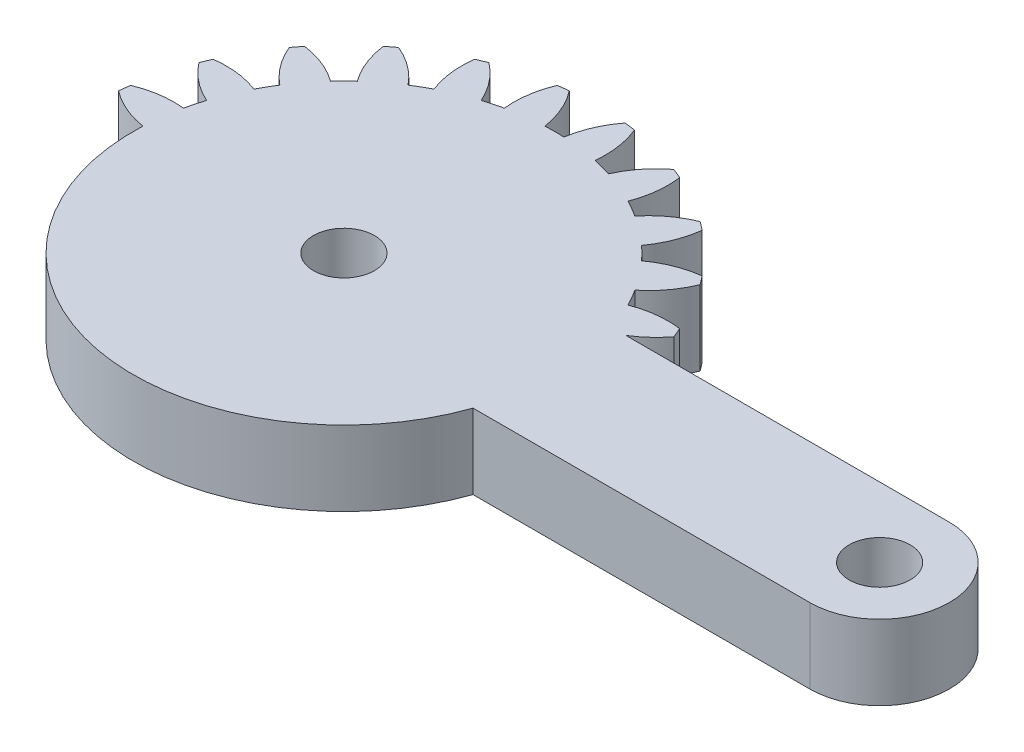
SolidWorks part; units mm, degrees
ref_plane "Front Plane" through (0, 0, 0) normal (0, 0, 1) x (1, 0, 0)
ref_plane "Top Plane" through (0, 0, 0) normal (0, 1, 0) x (1, 0, 0)
ref_plane "Right Plane" through (0, 0, 0) normal (1, 0, 0) x (0, 0, -1)
sketch "Sketch1" plane through (0, 0, 0) normal (0, 1, 0) x (1, 0, 0)
  line L0 (20.6437, 4) -> (2.0816, 4)
  line L1 (2.0816, -4) -> (20.6437, -4)
  arc A0 (2.0816, 4) -> (3.5217, 5.3071) centre (-0.7683, 8.5867) ccw
  arc A1 (3.5217, 5.3071) -> (3.2829, 5.8838) centre (-10.1063, 0) ccw
  arc A2 (3.2829, 5.8838) -> (0.6271, 5.5703) centre (2.5684, 0.5313) ccw
  arc A3 (0.6271, 5.5703) -> (0.0844, 6.5103) centre (-10.1063, 0) ccw
  arc A4 (0.0844, 6.5103) -> (1.6838, 8.6535) centre (-3.3089, 10.711) ccw
  arc A5 (1.6838, 8.6535) -> (1.3038, 9.1487) centre (-10.1063, 0) ccw
  arc A6 (1.3038, 9.1487) -> (-1.1803, 8.1585) centre (1.999, 3.7936) ccw
  arc A7 (-1.1803, 8.1585) -> (-1.9479, 8.926) centre (-10.1063, 0) ccw
  arc A8 (-1.9479, 8.926) -> (-0.9576, 11.4102) centre (-6.3127, 12.1053) ccw
  arc A9 (-0.9576, 11.4102) -> (-1.4528, 11.7901) centre (-10.1063, 0) ccw
  arc A10 (-1.4528, 11.7901) -> (-3.596, 10.1907) centre (0.6046, 6.7975) ccw
  arc A11 (-3.596, 10.1907) -> (-4.5361, 10.7334) centre (-10.1063, 0) ccw
  arc A12 (-4.5361, 10.7334) -> (-4.2225, 13.3892) centre (-9.5751, 12.6747) ccw
  arc A13 (-4.2225, 13.3892) -> (-4.7992, 13.6281) centre (-10.1063, 0) ccw
  arc A14 (-4.7992, 13.6281) -> (-6.4554, 11.5285) centre (-1.5196, 9.3381) ccw
  arc A15 (-6.4554, 11.5285) -> (-7.5039, 11.8094) centre (-10.1063, 0) ccw
  arc A16 (-7.5039, 11.8094) -> (-7.8884, 14.4558) centre (-12.8736, 12.3803) ccw
  arc A17 (-7.8884, 14.4558) -> (-8.5072, 14.5373) centre (-10.1063, 0) ccw
  arc A18 (-8.5072, 14.5373) -> (-9.5636, 12.0806) centre (-4.2291, 11.2423) ccw
  arc A19 (-9.5636, 12.0806) -> (-10.6491, 12.0806) centre (-10.1063, 0) ccw
  arc A20 (-10.6491, 12.0806) -> (-11.7054, 14.5373) centre (-15.9836, 11.2423) ccw
  arc A21 (-11.7054, 14.5373) -> (-12.3243, 14.4558) centre (-10.1063, 0) ccw
  arc A22 (-12.3243, 14.4558) -> (-12.7088, 11.8094) centre (-7.3391, 12.3803) ccw
  arc A23 (-12.7088, 11.8094) -> (-13.7573, 11.5285) centre (-10.1063, 0) ccw
  arc A24 (-13.7573, 11.5285) -> (-15.4135, 13.6281) centre (-18.6931, 9.3381) ccw
  arc A25 (-15.4135, 13.6281) -> (-15.9901, 13.3892) centre (-10.1063, 0) ccw
  arc A26 (-15.9901, 13.3892) -> (-15.6766, 10.7334) centre (-10.6376, 12.6747) ccw
  arc A27 (-15.6766, 10.7334) -> (-16.6166, 10.1907) centre (-10.1063, 0) ccw
  arc A28 (-16.6166, 10.1907) -> (-18.7599, 11.7901) centre (-20.8173, 6.7975) ccw
  arc A29 (-18.7599, 11.7901) -> (-19.255, 11.4102) centre (-10.1063, 0) ccw
  arc A30 (-19.255, 11.4102) -> (-18.2648, 8.926) centre (-13.9, 12.1053) ccw
  arc A31 (-18.2648, 8.926) -> (-19.0324, 8.1585) centre (-10.1063, 0) ccw
  arc A32 (-19.0324, 8.1585) -> (-21.5165, 9.1487) centre (-22.2117, 3.7936) ccw
  arc A33 (-21.5165, 9.1487) -> (-21.8965, 8.6535) centre (-10.1063, 0) ccw
  arc A34 (-21.8965, 8.6535) -> (-20.2971, 6.5103) centre (-16.9038, 10.711) ccw
  arc A35 (-20.2971, 6.5103) -> (-20.8398, 5.5703) centre (-10.1063, 0) ccw
  arc A36 (-20.8398, 5.5703) -> (-23.4956, 5.8838) centre (-22.7811, 0.5313) ccw
  arc A37 (-23.4956, 5.8838) -> (-23.7344, 5.3071) centre (-10.1063, 0) ccw
  arc A38 (-23.7344, 5.3071) -> (-21.6348, 3.6509) centre (-19.4444, 8.5867) ccw
  arc A39 (-21.6348, 3.6509) -> (-21.9157, 2.6025) centre (-10.1063, 0) ccw
  arc A40 (-21.9157, 2.6025) -> (-24.5622, 2.2179) centre (-22.4867, -2.7673) ccw
  arc A41 (-24.5622, 2.2179) -> (-24.6437, 1.5991) centre (-10.1063, 0) ccw
  arc A42 (-24.6437, 1.5991) -> (-22.1869, 0.5427) centre (-21.3486, 5.8773) ccw
  arc A43 (-22.1869, 0.5427) -> (-22.1869, -0.5427) centre (-10.1063, 0) ccw
  arc A44 (-22.1869, -0.5427) -> (-24.6437, -1.5991) centre (-21.3486, -5.8773) ccw
  arc A45 (-24.6437, -1.5991) -> (-24.5622, -2.2179) centre (-10.1063, 0) ccw
  arc A46 (-24.5622, -2.2179) -> (-21.9157, -2.6025) centre (-22.4867, 2.7673) ccw
  arc A47 (-21.9157, -2.6025) -> (-21.6348, -3.6509) centre (-10.1063, 0) ccw
  arc A48 (-21.6348, -3.6509) -> (-23.7344, -5.3071) centre (-19.4444, -8.5867) ccw
  arc A49 (-23.7344, -5.3071) -> (-23.4956, -5.8838) centre (-10.1063, 0) ccw
  arc A50 (-23.4956, -5.8838) -> (-20.8398, -5.5703) centre (-22.7811, -0.5313) ccw
  arc A51 (-20.8398, -5.5703) -> (-20.2971, -6.5103) centre (-10.1063, 0) ccw
  arc A52 (-20.2971, -6.5103) -> (-21.8965, -8.6535) centre (-16.9038, -10.711) ccw
  arc A53 (-21.8965, -8.6535) -> (-21.5165, -9.1487) centre (-10.1063, 0) ccw
  arc A54 (-21.5165, -9.1487) -> (-19.0324, -8.1585) centre (-22.2117, -3.7936) ccw
  arc A55 (-19.0324, -8.1585) -> (-18.2648, -8.926) centre (-10.1063, 0) ccw
  arc A56 (-18.2648, -8.926) -> (-19.255, -11.4102) centre (-13.9, -12.1053) ccw
  arc A57 (-19.255, -11.4102) -> (-18.7599, -11.7901) centre (-10.1063, 0) ccw
  arc A58 (-18.7599, -11.7901) -> (-16.6166, -10.1907) centre (-20.8173, -6.7975) ccw
  arc A59 (-16.6166, -10.1907) -> (-15.6766, -10.7334) centre (-10.1063, 0) ccw
  arc A60 (-15.6766, -10.7334) -> (-15.9901, -13.3892) centre (-10.6376, -12.6747) ccw
  arc A61 (-15.9901, -13.3892) -> (-15.4135, -13.6281) centre (-10.1063, 0) ccw
  arc A62 (-15.4135, -13.6281) -> (-13.7573, -11.5285) centre (-18.6931, -9.3381) ccw
  arc A63 (-13.7573, -11.5285) -> (-12.7088, -11.8094) centre (-10.1063, 0) ccw
  arc A64 (-12.7088, -11.8094) -> (-12.3243, -14.4558) centre (-7.3391, -12.3803) ccw
  arc A65 (-12.3243, -14.4558) -> (-11.7054, -14.5373) centre (-10.1063, 0) ccw
  arc A66 (-11.7054, -14.5373) -> (-10.6491, -12.0806) centre (-15.9836, -11.2423) ccw
  arc A67 (-10.6491, -12.0806) -> (-9.5636, -12.0806) centre (-10.1063, 0) ccw
  arc A68 (-9.5636, -12.0806) -> (-8.5072, -14.5373) centre (-4.2291, -11.2423) ccw
  arc A69 (-8.5072, -14.5373) -> (-7.8884, -14.4558) centre (-10.1063, 0) ccw
  arc A70 (-7.8884, -14.4558) -> (-7.5039, -11.8094) centre (-12.8736, -12.3803) ccw
  arc A71 (-7.5039, -11.8094) -> (-6.4554, -11.5285) centre (-10.1063, 0) ccw
  arc A72 (-6.4554, -11.5285) -> (-4.7992, -13.6281) centre (-1.5196, -9.3381) ccw
  arc A73 (-4.7992, -13.6281) -> (-4.2225, -13.3892) centre (-10.1063, 0) ccw
  arc A74 (-4.2225, -13.3892) -> (-4.5361, -10.7334) centre (-9.5751, -12.6747) ccw
  arc A75 (-4.5361, -10.7334) -> (-3.596, -10.1907) centre (-10.1063, 0) ccw
  arc A76 (-3.596, -10.1907) -> (-1.4528, -11.7901) centre (0.6046, -6.7975) ccw
  arc A77 (-1.4528, -11.7901) -> (-0.9576, -11.4102) centre (-10.1063, 0) ccw
  arc A78 (-0.9576, -11.4102) -> (-1.9479, -8.926) centre (-6.3127, -12.1053) ccw
  arc A79 (-1.9479, -8.926) -> (-1.1803, -8.1585) centre (-10.1063, 0) ccw
  arc A80 (-1.1803, -8.1585) -> (1.3038, -9.1487) centre (1.999, -3.7936) ccw
  arc A81 (1.3038, -9.1487) -> (1.6838, -8.6535) centre (-10.1063, 0) ccw
  arc A82 (1.6838, -8.6535) -> (0.0844, -6.5103) centre (-3.3089, -10.711) ccw
  arc A83 (0.0844, -6.5103) -> (0.6271, -5.5703) centre (-10.1063, 0) ccw
  arc A84 (0.6271, -5.5703) -> (3.2829, -5.8838) centre (2.5684, -0.5313) ccw
  arc A85 (3.2829, -5.8838) -> (3.5217, -5.3071) centre (-10.1063, 0) ccw
  arc A86 (3.5217, -5.3071) -> (2.0816, -4) centre (-0.7683, -8.5867) ccw
  arc A87 (20.6437, -4) -> (20.6437, 4) centre (20.6437, 0) ccw
  circle A88 centre (-10.1063, 0) radius 1.75
  circle A89 centre (20.6437, 0) radius 1.75
  dimension "D1" = 3.5
  dimension "D2" = 3.5
extrude "Boss-Extrude1" add sketch "Sketch1" along normal blind 4.3
sketch "Sketch2" plane through (0, 4.3, 0) normal (0, 1, 0) x (1, 0, 0)
  line L0 (2.0816, -4) -> (1.3057, -4)
  line L2 (20.6437, 4) -> (2.0816, 4)
  line L3 (2.0816, -4) -> (20.6437, -4)
  line L4 (20.6437, 4) -> (2.0816, 4)
  line L5 (2.0816, -4) -> (20.6437, -4)
  circle A0 centre (-10.1063, 0) radius 12.0927
  arc A88 (20.6437, -4) -> (20.6437, 4) centre (20.6437, 0) ccw
  arc A89 (2.0816, 4) -> (3.5217, 5.3071) centre (-0.7683, 8.5867) ccw
  arc A90 (3.5217, 5.3071) -> (3.2829, 5.8838) centre (-10.1063, 0) ccw
  arc A91 (3.2829, 5.8838) -> (0.6271, 5.5703) centre (2.5684, 0.5313) ccw
  arc A92 (0.6271, 5.5703) -> (0.0844, 6.5103) centre (-10.1063, 0) ccw
  arc A93 (0.0844, 6.5103) -> (1.6838, 8.6535) centre (-3.3089, 10.711) ccw
  arc A94 (1.6838, 8.6535) -> (1.3038, 9.1487) centre (-10.1063, 0) ccw
  arc A95 (1.3038, 9.1487) -> (-1.1803, 8.1585) centre (1.999, 3.7936) ccw
  arc A96 (-1.1803, 8.1585) -> (-1.9479, 8.926) centre (-10.1063, 0) ccw
  arc A97 (-1.9479, 8.926) -> (-0.9576, 11.4102) centre (-6.3127, 12.1053) ccw
  arc A98 (-0.9576, 11.4102) -> (-1.4528, 11.7901) centre (-10.1063, 0) ccw
  arc A99 (-1.4528, 11.7901) -> (-3.596, 10.1907) centre (0.6046, 6.7975) ccw
  arc A100 (-3.596, 10.1907) -> (-4.5361, 10.7334) centre (-10.1063, 0) ccw
  arc A101 (-4.5361, 10.7334) -> (-4.2225, 13.3892) centre (-9.5751, 12.6747) ccw
  arc A102 (-4.2225, 13.3892) -> (-4.7992, 13.6281) centre (-10.1063, 0) ccw
  arc A103 (-4.7992, 13.6281) -> (-6.4554, 11.5285) centre (-1.5196, 9.3381) ccw
  arc A104 (-6.4554, 11.5285) -> (-7.5039, 11.8094) centre (-10.1063, 0) ccw
  arc A105 (-7.5039, 11.8094) -> (-7.8884, 14.4558) centre (-12.8736, 12.3803) ccw
  arc A106 (-7.8884, 14.4558) -> (-8.5072, 14.5373) centre (-10.1063, 0) ccw
  arc A107 (-8.5072, 14.5373) -> (-9.5636, 12.0806) centre (-4.2291, 11.2423) ccw
  arc A108 (-9.5636, 12.0806) -> (-10.6491, 12.0806) centre (-10.1063, 0) ccw
  arc A109 (-10.6491, 12.0806) -> (-11.7054, 14.5373) centre (-15.9836, 11.2423) ccw
  arc A110 (-11.7054, 14.5373) -> (-12.3243, 14.4558) centre (-10.1063, 0) ccw
  arc A111 (-12.3243, 14.4558) -> (-12.7088, 11.8094) centre (-7.3391, 12.3803) ccw
  arc A112 (-12.7088, 11.8094) -> (-13.7573, 11.5285) centre (-10.1063, 0) ccw
  arc A113 (-13.7573, 11.5285) -> (-15.4135, 13.6281) centre (-18.6931, 9.3381) ccw
  arc A114 (-15.4135, 13.6281) -> (-15.9901, 13.3892) centre (-10.1063, 0) ccw
  arc A115 (-15.9901, 13.3892) -> (-15.6766, 10.7334) centre (-10.6376, 12.6747) ccw
  arc A116 (-15.6766, 10.7334) -> (-16.6166, 10.1907) centre (-10.1063, 0) ccw
  arc A117 (-16.6166, 10.1907) -> (-18.7599, 11.7901) centre (-20.8173, 6.7975) ccw
  arc A118 (-18.7599, 11.7901) -> (-19.255, 11.4102) centre (-10.1063, 0) ccw
  arc A119 (-19.255, 11.4102) -> (-18.2648, 8.926) centre (-13.9, 12.1053) ccw
  arc A120 (-18.2648, 8.926) -> (-19.0324, 8.1585) centre (-10.1063, 0) ccw
  arc A121 (-19.0324, 8.1585) -> (-21.5165, 9.1487) centre (-22.2117, 3.7936) ccw
  arc A122 (-21.5165, 9.1487) -> (-21.8965, 8.6535) centre (-10.1063, 0) ccw
  arc A123 (-21.8965, 8.6535) -> (-20.2971, 6.5103) centre (-16.9038, 10.711) ccw
  arc A124 (-20.2971, 6.5103) -> (-20.8398, 5.5703) centre (-10.1063, 0) ccw
  arc A125 (-20.8398, 5.5703) -> (-23.4956, 5.8838) centre (-22.7811, 0.5313) ccw
  arc A126 (-23.4956, 5.8838) -> (-23.7344, 5.3071) centre (-10.1063, 0) ccw
  arc A127 (-23.7344, 5.3071) -> (-21.6348, 3.6509) centre (-19.4444, 8.5867) ccw
  arc A128 (-21.6348, 3.6509) -> (-21.9157, 2.6025) centre (-10.1063, 0) ccw
  arc A129 (-21.9157, 2.6025) -> (-24.5622, 2.2179) centre (-22.4867, -2.7673) ccw
  arc A130 (-24.5622, 2.2179) -> (-24.6437, 1.5991) centre (-10.1063, 0) ccw
  arc A131 (-24.6437, 1.5991) -> (-22.1869, 0.5427) centre (-21.3486, 5.8773) ccw
  arc A132 (-22.1869, 0.5427) -> (-22.1869, -0.5427) centre (-10.1063, 0) ccw
  arc A133 (-22.1869, -0.5427) -> (-24.6437, -1.5991) centre (-21.3486, -5.8773) ccw
  arc A134 (-24.6437, -1.5991) -> (-24.5622, -2.2179) centre (-10.1063, 0) ccw
  arc A135 (-24.5622, -2.2179) -> (-21.9157, -2.6025) centre (-22.4867, 2.7673) ccw
  arc A136 (-21.9157, -2.6025) -> (-21.6348, -3.6509) centre (-10.1063, 0) ccw
  arc A137 (-21.6348, -3.6509) -> (-23.7344, -5.3071) centre (-19.4444, -8.5867) ccw
  arc A138 (-23.7344, -5.3071) -> (-23.4956, -5.8838) centre (-10.1063, 0) ccw
  arc A139 (-23.4956, -5.8838) -> (-20.8398, -5.5703) centre (-22.7811, -0.5313) ccw
  arc A140 (-20.8398, -5.5703) -> (-20.2971, -6.5103) centre (-10.1063, 0) ccw
  arc A141 (-20.2971, -6.5103) -> (-21.8965, -8.6535) centre (-16.9038, -10.711) ccw
  arc A142 (-21.8965, -8.6535) -> (-21.5165, -9.1487) centre (-10.1063, 0) ccw
  arc A143 (-21.5165, -9.1487) -> (-19.0324, -8.1585) centre (-22.2117, -3.7936) ccw
  arc A144 (-19.0324, -8.1585) -> (-18.2648, -8.926) centre (-10.1063, 0) ccw
  arc A145 (-18.2648, -8.926) -> (-19.255, -11.4102) centre (-13.9, -12.1053) ccw
  arc A146 (-19.255, -11.4102) -> (-18.7599, -11.7901) centre (-10.1063, 0) ccw
  arc A147 (-18.7599, -11.7901) -> (-16.6166, -10.1907) centre (-20.8173, -6.7975) ccw
  arc A148 (-16.6166, -10.1907) -> (-15.6766, -10.7334) centre (-10.1063, 0) ccw
  arc A149 (-15.6766, -10.7334) -> (-15.9901, -13.3892) centre (-10.6376, -12.6747) ccw
  arc A150 (-15.9901, -13.3892) -> (-15.4135, -13.6281) centre (-10.1063, 0) ccw
  arc A151 (-15.4135, -13.6281) -> (-13.7573, -11.5285) centre (-18.6931, -9.3381) ccw
  arc A152 (-13.7573, -11.5285) -> (-12.7088, -11.8094) centre (-10.1063, 0) ccw
  arc A153 (-12.7088, -11.8094) -> (-12.3243, -14.4558) centre (-7.3391, -12.3803) ccw
  arc A154 (-12.3243, -14.4558) -> (-11.7054, -14.5373) centre (-10.1063, 0) ccw
  arc A155 (-11.7054, -14.5373) -> (-10.6491, -12.0806) centre (-15.9836, -11.2423) ccw
  arc A156 (-10.6491, -12.0806) -> (-9.5636, -12.0806) centre (-10.1063, 0) ccw
  arc A157 (-9.5636, -12.0806) -> (-8.5072, -14.5373) centre (-4.2291, -11.2423) ccw
  arc A158 (-8.5072, -14.5373) -> (-7.8884, -14.4558) centre (-10.1063, 0) ccw
  arc A159 (-7.8884, -14.4558) -> (-7.5039, -11.8094) centre (-12.8736, -12.3803) ccw
  arc A160 (-7.5039, -11.8094) -> (-6.4554, -11.5285) centre (-10.1063, 0) ccw
  arc A161 (-6.4554, -11.5285) -> (-4.7992, -13.6281) centre (-1.5196, -9.3381) ccw
  arc A162 (-4.7992, -13.6281) -> (-4.2225, -13.3892) centre (-10.1063, 0) ccw
  arc A163 (-4.2225, -13.3892) -> (-4.5361, -10.7334) centre (-9.5751, -12.6747) ccw
  arc A164 (-4.5361, -10.7334) -> (-3.596, -10.1907) centre (-10.1063, 0) ccw
  arc A165 (-3.596, -10.1907) -> (-1.4528, -11.7901) centre (0.6046, -6.7975) ccw
  arc A166 (-1.4528, -11.7901) -> (-0.9576, -11.4102) centre (-10.1063, 0) ccw
  arc A167 (-0.9576, -11.4102) -> (-1.9479, -8.926) centre (-6.3127, -12.1053) ccw
  arc A168 (-1.9479, -8.926) -> (-1.1803, -8.1585) centre (-10.1063, 0) ccw
  arc A169 (-1.1803, -8.1585) -> (1.3038, -9.1487) centre (1.999, -3.7936) ccw
  arc A170 (1.3038, -9.1487) -> (1.6838, -8.6535) centre (-10.1063, 0) ccw
  arc A171 (1.6838, -8.6535) -> (0.0844, -6.5103) centre (-3.3089, -10.711) ccw
  arc A172 (0.0844, -6.5103) -> (0.6271, -5.5703) centre (-10.1063, 0) ccw
  arc A173 (0.6271, -5.5703) -> (3.2829, -5.8838) centre (2.5684, -0.5313) ccw
  arc A174 (3.2829, -5.8838) -> (3.5217, -5.3071) centre (-10.1063, 0) ccw
  arc A175 (3.5217, -5.3071) -> (2.0816, -4) centre (-0.7683, -8.5867) ccw
  arc A176 (20.6437, -4) -> (20.6437, 4) centre (20.6437, 0) ccw
  arc A177 (2.0816, 4) -> (3.5217, 5.3071) centre (-0.7683, 8.5867) ccw
  arc A178 (3.5217, 5.3071) -> (3.2829, 5.8838) centre (-10.1063, 0) ccw
  arc A179 (3.2829, 5.8838) -> (0.6271, 5.5703) centre (2.5684, 0.5313) ccw
  arc A180 (0.6271, 5.5703) -> (0.0844, 6.5103) centre (-10.1063, 0) ccw
  arc A181 (0.0844, 6.5103) -> (1.6838, 8.6535) centre (-3.3089, 10.711) ccw
  arc A182 (1.6838, 8.6535) -> (1.3038, 9.1487) centre (-10.1063, 0) ccw
  arc A183 (1.3038, 9.1487) -> (-1.1803, 8.1585) centre (1.999, 3.7936) ccw
  arc A184 (-1.1803, 8.1585) -> (-1.9479, 8.926) centre (-10.1063, 0) ccw
  arc A185 (-1.9479, 8.926) -> (-0.9576, 11.4102) centre (-6.3127, 12.1053) ccw
  arc A186 (-0.9576, 11.4102) -> (-1.4528, 11.7901) centre (-10.1063, 0) ccw
  arc A187 (-1.4528, 11.7901) -> (-3.596, 10.1907) centre (0.6046, 6.7975) ccw
  arc A188 (-3.596, 10.1907) -> (-4.5361, 10.7334) centre (-10.1063, 0) ccw
  arc A189 (-4.5361, 10.7334) -> (-4.2225, 13.3892) centre (-9.5751, 12.6747) ccw
  arc A190 (-4.2225, 13.3892) -> (-4.7992, 13.6281) centre (-10.1063, 0) ccw
  arc A191 (-4.7992, 13.6281) -> (-6.4554, 11.5285) centre (-1.5196, 9.3381) ccw
  arc A192 (-6.4554, 11.5285) -> (-7.5039, 11.8094) centre (-10.1063, 0) ccw
  arc A193 (-7.5039, 11.8094) -> (-7.8884, 14.4558) centre (-12.8736, 12.3803) ccw
  arc A194 (-7.8884, 14.4558) -> (-8.5072, 14.5373) centre (-10.1063, 0) ccw
  arc A195 (-8.5072, 14.5373) -> (-9.5636, 12.0806) centre (-4.2291, 11.2423) ccw
  arc A196 (-9.5636, 12.0806) -> (-10.6491, 12.0806) centre (-10.1063, 0) ccw
  arc A197 (-10.6491, 12.0806) -> (-11.7054, 14.5373) centre (-15.9836, 11.2423) ccw
  arc A198 (-11.7054, 14.5373) -> (-12.3243, 14.4558) centre (-10.1063, 0) ccw
  arc A199 (-12.3243, 14.4558) -> (-12.7088, 11.8094) centre (-7.3391, 12.3803) ccw
  arc A200 (-12.7088, 11.8094) -> (-13.7573, 11.5285) centre (-10.1063, 0) ccw
  arc A201 (-13.7573, 11.5285) -> (-15.4135, 13.6281) centre (-18.6931, 9.3381) ccw
  arc A202 (-15.4135, 13.6281) -> (-15.9901, 13.3892) centre (-10.1063, 0) ccw
  arc A203 (-15.9901, 13.3892) -> (-15.6766, 10.7334) centre (-10.6376, 12.6747) ccw
  arc A204 (-15.6766, 10.7334) -> (-16.6166, 10.1907) centre (-10.1063, 0) ccw
  arc A205 (-16.6166, 10.1907) -> (-18.7599, 11.7901) centre (-20.8173, 6.7975) ccw
  arc A206 (-18.7599, 11.7901) -> (-19.255, 11.4102) centre (-10.1063, 0) ccw
  arc A207 (-19.255, 11.4102) -> (-18.2648, 8.926) centre (-13.9, 12.1053) ccw
  arc A208 (-18.2648, 8.926) -> (-19.0324, 8.1585) centre (-10.1063, 0) ccw
  arc A209 (-19.0324, 8.1585) -> (-21.5165, 9.1487) centre (-22.2117, 3.7936) ccw
  arc A210 (-21.5165, 9.1487) -> (-21.8965, 8.6535) centre (-10.1063, 0) ccw
  arc A211 (-21.8965, 8.6535) -> (-20.2971, 6.5103) centre (-16.9038, 10.711) ccw
  arc A212 (-20.2971, 6.5103) -> (-20.8398, 5.5703) centre (-10.1063, 0) ccw
  arc A213 (-20.8398, 5.5703) -> (-23.4956, 5.8838) centre (-22.7811, 0.5313) ccw
  arc A214 (-23.4956, 5.8838) -> (-23.7344, 5.3071) centre (-10.1063, 0) ccw
  arc A215 (-23.7344, 5.3071) -> (-21.6348, 3.6509) centre (-19.4444, 8.5867) ccw
  arc A216 (-21.6348, 3.6509) -> (-21.9157, 2.6025) centre (-10.1063, 0) ccw
  arc A217 (-21.9157, 2.6025) -> (-24.5622, 2.2179) centre (-22.4867, -2.7673) ccw
  arc A218 (-24.5622, 2.2179) -> (-24.6437, 1.5991) centre (-10.1063, 0) ccw
  arc A219 (-24.6437, 1.5991) -> (-22.1869, 0.5427) centre (-21.3486, 5.8773) ccw
  arc A220 (-22.1869, 0.5427) -> (-22.1869, -0.5427) centre (-10.1063, 0) ccw
  arc A221 (-22.1869, -0.5427) -> (-24.6437, -1.5991) centre (-21.3486, -5.8773) ccw
  arc A222 (-24.6437, -1.5991) -> (-24.5622, -2.2179) centre (-10.1063, 0) ccw
  arc A223 (-24.5622, -2.2179) -> (-21.9157, -2.6025) centre (-22.4867, 2.7673) ccw
  arc A224 (-21.9157, -2.6025) -> (-21.6348, -3.6509) centre (-10.1063, 0) ccw
  arc A225 (-21.6348, -3.6509) -> (-23.7344, -5.3071) centre (-19.4444, -8.5867) ccw
  arc A226 (-23.7344, -5.3071) -> (-23.4956, -5.8838) centre (-10.1063, 0) ccw
  arc A227 (-23.4956, -5.8838) -> (-20.8398, -5.5703) centre (-22.7811, -0.5313) ccw
  arc A228 (-20.8398, -5.5703) -> (-20.2971, -6.5103) centre (-10.1063, 0) ccw
  arc A229 (-20.2971, -6.5103) -> (-21.8965, -8.6535) centre (-16.9038, -10.711) ccw
  arc A230 (-21.8965, -8.6535) -> (-21.5165, -9.1487) centre (-10.1063, 0) ccw
  arc A231 (-21.5165, -9.1487) -> (-19.0324, -8.1585) centre (-22.2117, -3.7936) ccw
  arc A232 (-19.0324, -8.1585) -> (-18.2648, -8.926) centre (-10.1063, 0) ccw
  arc A233 (-18.2648, -8.926) -> (-19.255, -11.4102) centre (-13.9, -12.1053) ccw
  arc A234 (-19.255, -11.4102) -> (-18.7599, -11.7901) centre (-10.1063, 0) ccw
  arc A235 (-18.7599, -11.7901) -> (-16.6166, -10.1907) centre (-20.8173, -6.7975) ccw
  arc A236 (-16.6166, -10.1907) -> (-15.6766, -10.7334) centre (-10.1063, 0) ccw
  arc A237 (-15.6766, -10.7334) -> (-15.9901, -13.3892) centre (-10.6376, -12.6747) ccw
  arc A238 (-15.9901, -13.3892) -> (-15.4135, -13.6281) centre (-10.1063, 0) ccw
  arc A239 (-15.4135, -13.6281) -> (-13.7573, -11.5285) centre (-18.6931, -9.3381) ccw
  arc A240 (-13.7573, -11.5285) -> (-12.7088, -11.8094) centre (-10.1063, 0) ccw
  arc A241 (-12.7088, -11.8094) -> (-12.3243, -14.4558) centre (-7.3391, -12.3803) ccw
  arc A242 (-12.3243, -14.4558) -> (-11.7054, -14.5373) centre (-10.1063, 0) ccw
  arc A243 (-11.7054, -14.5373) -> (-10.6491, -12.0806) centre (-15.9836, -11.2423) ccw
  arc A244 (-10.6491, -12.0806) -> (-9.5636, -12.0806) centre (-10.1063, 0) ccw
  arc A245 (-9.5636, -12.0806) -> (-8.5072, -14.5373) centre (-4.2291, -11.2423) ccw
  arc A246 (-8.5072, -14.5373) -> (-7.8884, -14.4558) centre (-10.1063, 0) ccw
  arc A247 (-7.8884, -14.4558) -> (-7.5039, -11.8094) centre (-12.8736, -12.3803) ccw
  arc A248 (-7.5039, -11.8094) -> (-6.4554, -11.5285) centre (-10.1063, 0) ccw
  arc A249 (-6.4554, -11.5285) -> (-4.7992, -13.6281) centre (-1.5196, -9.3381) ccw
  arc A250 (-4.7992, -13.6281) -> (-4.2225, -13.3892) centre (-10.1063, 0) ccw
  arc A251 (-4.2225, -13.3892) -> (-4.5361, -10.7334) centre (-9.5751, -12.6747) ccw
  arc A252 (-4.5361, -10.7334) -> (-3.596, -10.1907) centre (-10.1063, 0) ccw
  arc A253 (-3.596, -10.1907) -> (-1.4528, -11.7901) centre (0.6046, -6.7975) ccw
  arc A254 (-1.4528, -11.7901) -> (-0.9576, -11.4102) centre (-10.1063, 0) ccw
  arc A255 (-0.9576, -11.4102) -> (-1.9479, -8.926) centre (-6.3127, -12.1053) ccw
  arc A256 (-1.9479, -8.926) -> (-1.1803, -8.1585) centre (-10.1063, 0) ccw
  arc A257 (-1.1803, -8.1585) -> (1.3038, -9.1487) centre (1.999, -3.7936) ccw
  arc A258 (1.3038, -9.1487) -> (1.6838, -8.6535) centre (-10.1063, 0) ccw
  arc A259 (1.6838, -8.6535) -> (0.0844, -6.5103) centre (-3.3089, -10.711) ccw
  arc A260 (0.0844, -6.5103) -> (0.6271, -5.5703) centre (-10.1063, 0) ccw
  arc A261 (0.6271, -5.5703) -> (3.2829, -5.8838) centre (2.5684, -0.5313) ccw
  arc A262 (3.2829, -5.8838) -> (3.5217, -5.3071) centre (-10.1063, 0) ccw
  arc A263 (3.5217, -5.3071) -> (2.0816, -4) centre (-0.7683, -8.5867) ccw
  dimension "D1" = 0
extrude "Cut-Extrude1" cut sketch "Sketch2" against normal blind 10 contours A222 A223 A0 A221 | A226 A227 A0 A225 | A230 A231 A0 A229 | A234 A235 A0 A233 | A238 A239 A0 A237 | A242 A243 A0 A241 | A246 A247 A0 A245 | A250 A251 A0 A249 | A254 A255 A0 A253 | A258 A259 A0 A257 | A262 A263 L0 A0 A261 region at (2.066, 4.3, 5.0775) region at (0.3325, 4.3, 8.01) region at (-2.0963, 4.3, 10.4389) region at (-5.071, 4.3, 12.1563) region at (-8.3889, 4.3, 13.0454) region at (-11.8238, 4.3, 13.0454) region at (-15.1417, 4.3, 12.1563) region at (-18.1164, 4.3, 10.4389) region at (-20.5452, 4.3, 8.01) region at (-22.2627, 4.3, 5.0353) region at (-23.1517, 4.3, 1.7175)
